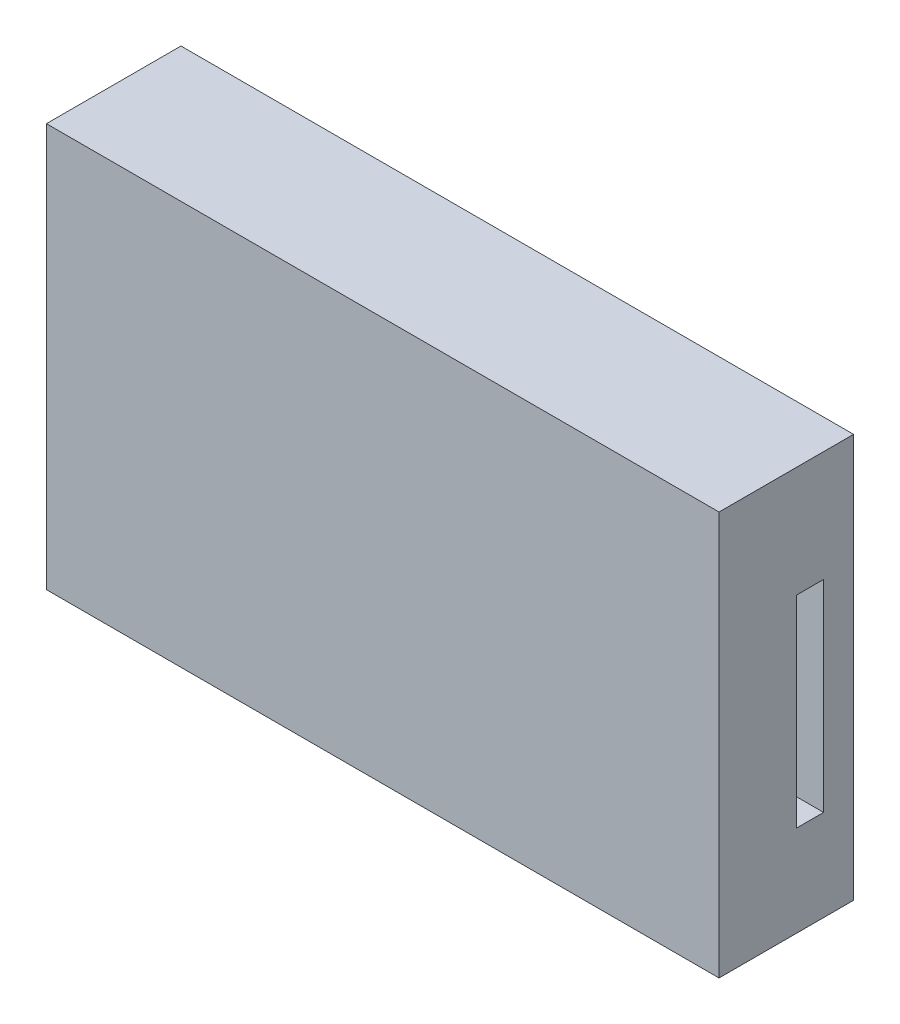
SolidWorks part; units mm, degrees
ref_plane "Front Plane" through (0, 0, 0) normal (0, 0, 1) x (1, 0, 0)
ref_plane "Top Plane" through (0, 0, 0) normal (0, 1, 0) x (1, 0, 0)
ref_plane "Right Plane" through (0, 0, 0) normal (1, 0, 0) x (0, 0, -1)
sketch "Sketch1" plane through (0, 0, 0) normal (0, 0, 1) x (1, 0, 0)
  line L1 (-25, 15) -> (25, 15)
  line L2 (-25, 15) -> (-25, -15)
  line L3 (-25, -15) -> (25, -15)
  line L4 (25, 15) -> (25, -15)
  line L5 (-25, 15) -> (25, -15) construction
  line L6 (-25, -15) -> (25, 15) construction
  point P0 (0, 0)
  dimension "D1" = 50
  dimension "D2" = 30
extrude "Boss-Extrude1" add sketch "Sketch1" along normal blind 10
shell "Shell4" thickness 2 removed face at (0, 0, 0)
ref_plane "Plane1" through (35, 0, 0) normal (1, 0, 0) x (0, 0, -1)
sketch "Sketch9" plane through (35, 0, 0) normal (1, 0, 0) x (0, 0, -1)
  line L1 (-4.226, 6.773) -> (-2.226, 6.773)
  line L2 (-4.226, 6.773) -> (-4.226, -8.227)
  line L3 (-4.226, -8.227) -> (-2.226, -8.227)
  line L4 (-2.226, 6.773) -> (-2.226, -8.227)
  line L5 (-4.226, 6.773) -> (-2.226, -8.227) construction
  line L6 (-4.226, -8.227) -> (-2.226, 6.773) construction
  point P0 (-3.226, -0.727)
extrude "Cut-Extrude5" cut sketch "Sketch9" against normal through all
ref_plane "Plane2" through (0, 25, 0) normal (0, 1, 0) x (1, 0, 0)
